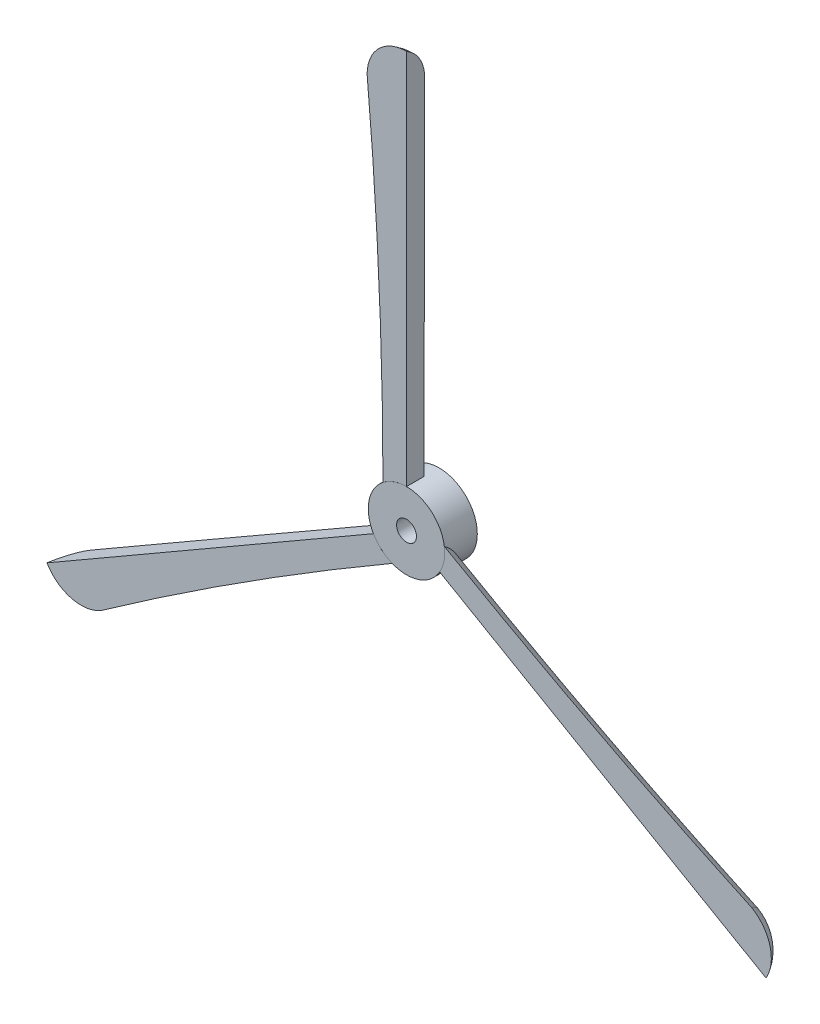
SolidWorks part; units mm, degrees
ref_plane "Plan de face" through (0, 0, 0) normal (0, 0, 1) x (1, 0, 0)
ref_plane "Plan de dessus" through (0, 0, 0) normal (0, 1, 0) x (1, 0, 0)
ref_plane "Plan de droite" through (0, 0, 0) normal (1, 0, 0) x (0, 0, -1)
sketch "Esquisse1" plane through (0, 0, 0) normal (0, 0, 1) x (1, 0, 0)
  circle A1 centre (0, 0) radius 10.5679
  circle A3 centre (0, 0) radius 10.5679
extrude "Boss.-Extru.1" add sketch "Esquisse1" along normal blind 9 contours A1 region at (0, 0, 0)
hole_wizard "Dégagement M51" positions "Esquisse3D2" profile "Esquisse2" hole size "M5" standard "ISO" end condition through all
sketch3d "Esquisse3D2"
  point P10 (0, 0, 0)
sketch "Esquisse2" plane through (0, 0, 0) normal (1, 0, 0) x (0, 1, 0)
  line L0 (0, 0) -> (0, 9)
  line L1 (0, 9) -> (2.75, 9)
  line L2 (2.75, 9) -> (2.75, 0)
  line L5 (2.75, 0) -> (0, 0)
  line L11 (0, -6.35) -> (0, 107.95) construction
  dimension "Diamètre du perçage jusqu'au prochain" = 5.5
  dimension "Profondeur du perçage jusqu'au prochain" = 9
sketch "Esquisse4" plane through (0, 0, 9) normal (0, 0, 1) x (1, 0, 0)
  line L0 (0, 0) -> (0, 114.75) construction
  line L1 (0, 0) -> (99.3764, -57.375) construction
  line L2 (0, 0) -> (-99.3764, -57.375) construction
  line L3 (0, 10.5679) -> (0, 114.75)
  circle A0 centre (0, 0) radius 114.75 construction
  circle A1 centre (0, 0) radius 10.5679 construction
  arc A2 (0, 114.75) -> (-10.8902, 103.8504) centre (0, 103.8598) ccw
  arc A3 (-10.8902, 103.8504) -> (-6.5083, 8.3261) centre (-1075.4991, 7.1512) cw
  arc A4 (-9.1521, -5.284) -> (-6.5083, 8.3261) centre (0, 0) ccw
  circle M5 centre (0, 0) radius 10.5679
  dimension "D1" = 229.5
  dimension "D2" = 120
  dimension "D3" = 120
extrude "Boss.-Extru.2" add sketch "Esquisse4" against normal blind 5 separate body contours A2 A3 L3 M5 region at (-4.1759, 66.35, 9)
fillet "Congé1" radius 10 2 edges at (-7.7039, 111.557, 4) (-7.6306, 56.1373, 4)
pattern_circular "Répétition circulaire6" count 3 every 120 about axis through (0, 0, 0) along (0, 0, 1) of bodies 103
